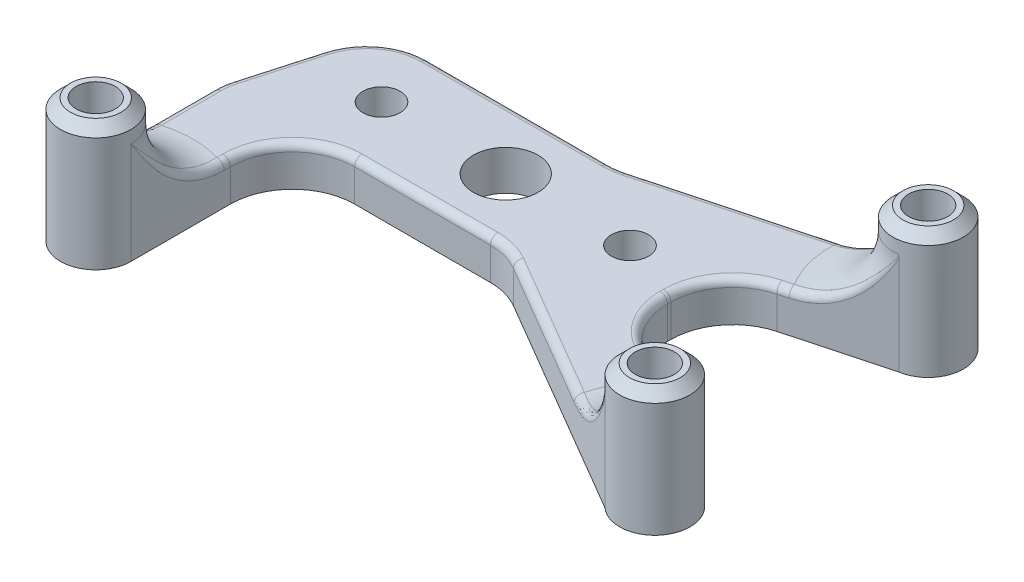
SolidWorks part; units mm, degrees
ref_plane "Front Plane" through (0, 0, 0) normal (0, 0, 1) x (1, 0, 0)
ref_plane "Top Plane" through (0, 0, 0) normal (0, 1, 0) x (1, 0, 0)
ref_plane "Right Plane" through (0, 0, 0) normal (1, 0, 0) x (0, 0, -1)
sketch "Sketch6" plane through (0, 0, 0) normal (0, 1, 0) x (1, 0, 0)
  line L1 (-19.05, -6.35) -> (19.05, -6.35)
  line L2 (-19.05, -6.35) -> (-19.05, 6.35)
  line L3 (-19.05, 6.35) -> (19.05, 6.35)
  line L4 (19.05, -6.35) -> (19.05, 6.35)
  line L5 (-19.05, -6.35) -> (19.05, 6.35) construction
  line L6 (-19.05, 6.35) -> (19.05, -6.35) construction
  point P0 (0, 0)
  dimension "D1" = 12.7
  dimension "D2" = 38.1
extrude "Boss-Extrude6" add sketch "Sketch6" along normal blind 3.175 separate body
sketch "Sketch4" plane through (0, 0, 0) normal (0, 1, 0) x (1, 0, 0)
  circle A0 centre (-19.05, -22.86) radius 3.6
  circle A1 centre (33.02, -17.78) radius 3.6
  circle A2 centre (33.02, 10.16) radius 3.6
  dimension "D1" = 7.2
  dimension "D2" = 7.2
  dimension "D3" = 7.2
  dimension "D4" = 52.07
  dimension "D5" = 5.08
  dimension "D6" = 27.94
  dimension "D7" = 10.16
  dimension "D8" = 33.02
extrude "Boss-Extrude5" add sketch "Sketch4" along normal blind 12.7
sketch "Sketch8" plane through (0, 0, 0) normal (0, 1, 0) x (1, 0, 0)
  line L2 (31.8384, 13.5606) -> (5.0632, 6.35)
  line L3 (19.05, 6.35) -> (-19.05, 6.35) construction
  line L4 (33.5862, 6.6048) -> (19.05, 2.6902)
  line L5 (19.05, -6.35) -> (19.05, 6.35) construction
  line L6 (19.05, 2.6902) -> (19.05, -6.35)
  line L7 (19.05, -6.35) -> (34.6277, -14.5589)
  line L8 (30.6114, -20.4556) -> (6.515, -6.35)
  line L9 (-19.05, -6.35) -> (19.05, -6.35) construction
  line L10 (6.515, -6.35) -> (-15.45, -6.35)
  line L11 (-15.45, -6.35) -> (-15.45, -22.86)
  line L12 (-22.65, -22.86) -> (-22.65, -6.35)
  line L13 (-22.65, -6.35) -> (-19.05, 6.35)
  line L14 (-19.05, 6.35) -> (5.0632, 6.35)
  circle A0 centre (33.02, 10.16) radius 3.6 construction
  arc A1 (33.5862, 6.6048) -> (31.8384, 13.5606) centre (33.02, 10.16) ccw
  circle A2 centre (33.02, -17.78) radius 3.6 construction
  arc A3 (34.6277, -14.5589) -> (30.6114, -20.4556) centre (33.02, -17.78) cw
  circle A4 centre (-19.05, -22.86) radius 3.6 construction
  arc A5 (-15.45, -22.86) -> (-22.65, -22.86) centre (-19.05, -22.86) cw
extrude "Boss-Extrude7" add sketch "Sketch8" along normal blind 4.064
fillet "Fillet1" radius 6.35 7 edges at (-15.45, 2.032, 6.35) (6.515, 2.032, 6.35) (19.05, 2.032, 6.35) (19.05, 2.032, -2.6902) (5.0632, 2.032, -6.35) (-22.65, 2.032, 6.35) (-19.05, 2.032, -6.35)
sketch "Sketch9" plane through (0, 4.064, 0) normal (0, 1, 0) x (1, 0, 0)
  circle A0 centre (-12.7, 0) radius 1.905
  circle A1 centre (12.7, 0) radius 1.905
  circle A2 centre (0, 0) radius 3.302
  dimension "D3" = 3.81
  dimension "D4" = 3.81
  dimension "D5" = 6.604
  dimension "D1" = 25.4
  dimension "D2" = 12.7
extrude "Cut-Extrude3" cut sketch "Sketch9" against normal through all
fillet "Fillet2" radius 6.35 3 edges at (-19.05, 4.064, 19.26) (30.0446, 4.064, 15.7534) (29.5285, 4.064, -9.2827)
sketch "Sketch10" plane through (0, 12.7, 0) normal (0, 1, 0) x (1, 0, 0)
  circle A0 centre (-19.05, -22.86) radius 2
  circle A1 centre (33.02, -17.78) radius 2
  circle A2 centre (33.02, 10.16) radius 2
  dimension "D1" = 4
  dimension "D2" = 4
  dimension "D3" = 4
extrude "Cut-Extrude4" cut sketch "Sketch10" against normal blind 5.7
chamfer "Chamfer1" distance 1.016 angle 45 3 edges at (33.02, 12.7, -6.56) (33.02, 12.7, 21.38) (-19.05, 12.7, 26.46)
fillet "Fillet3" radius 0.762 23 edges at (34.1822, 9.6509, 14.3242) (24.4655, 4.064, 9.2038) (33.042, 9.2814, -6.4582) (24.3677, 4.064, -4.1223) (20.3598, 4.064, -1.6865) (19.05, 4.064, 2.3472) (30.8667, 8.8079, -13.2989) (14.5002, 4.064, -8.8914) (5.0559, 4.064, -6.4048) (-22.65, 5.6615, 18.3911) (-22.65, 4.064, 10.4084) (-22.5895, 4.064, 6.3584) (-21.3842, 4.064, 1.8845) (-18.079, 4.064, -5.0655) (-15.45, 5.6615, 18.3911) (-15.45, 4.064, 13.142) (-13.5901, 4.064, 8.2099) (29.7882, 8.4666, 19.9737) (15.605, 4.064, 11.6711) (6.455, 4.064, 6.5713) (19.9631, 4.064, 5.7991) (-5.0133, 4.064, -6.35) (-2.1535, 4.064, 6.35)
sketch "Sketch11" plane through (0, 7, 0) normal (0, 1, 0) x (1, 0, 0)
  circle A0 centre (-19.05, -22.86) radius 1.5875
  circle A1 centre (33.02, -17.78) radius 1.5875
  circle A2 centre (33.02, 10.16) radius 1.5875
  dimension "D1" = 3.175
  dimension "D2" = 3.175
  dimension "D3" = 3.175
extrude "Cut-Extrude5" cut sketch "Sketch11" against normal through all
